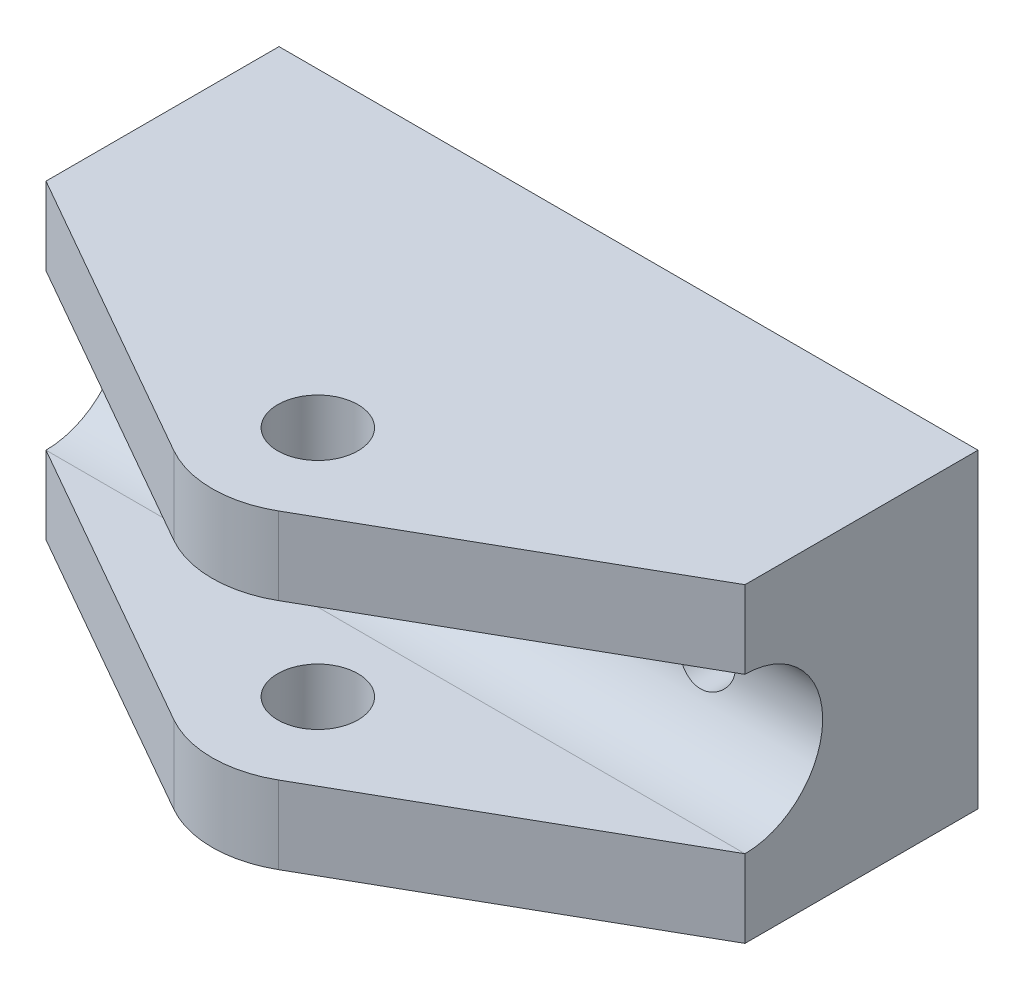
SolidWorks part; units mm, degrees
ref_plane "Front Plane" through (0, 0, 0) normal (0, 0, 1) x (1, 0, 0)
ref_plane "Top Plane" through (0, 0, 0) normal (0, 1, 0) x (1, 0, 0)
ref_plane "Right Plane" through (0, 0, 0) normal (1, 0, 0) x (0, 0, -1)
sketch "Sketch1" plane through (0, 0, 0) normal (0, 0, 1) x (1, 0, 0)
  line L1 (254.9308, 254) -> (197.7808, 254)
  line L2 (254.9308, 254) -> (254.9308, 228.6)
  line L3 (254.9308, 228.6) -> (197.7808, 228.6)
  line L4 (197.7808, 254) -> (197.7808, 228.6)
  line L5 (254.9308, 254) -> (197.7808, 228.6) construction
  line L6 (254.9308, 228.6) -> (197.7808, 254) construction
  line L11 (264.4558, 254) -> (-34.0111, 254) construction
  line L12 (264.4558, 228.6) -> (-34.0111, 228.6) construction
  line L13 (207.3058, 241.3) -> (245.4058, 241.3)
  circle A0 centre (245.4058, 241.3) radius 2.3813 construction
  circle A1 centre (207.3058, 241.3) radius 2.3813 construction
  circle A2 centre (245.4058, 241.3) radius 2.3813
  circle A3 centre (207.3058, 241.3) radius 2.3813
  point P6 (226.3558, 241.3)
  point P12 (226.3558, 241.3)
  dimension "D1" = 57.15
extrude "Boss-Extrude1" add sketch "Sketch1" along normal blind 34.036 contours L1 L4 L3 L2 A3 A2 region at (254.3054, 241.3, 0)
sketch "Sketch2" plane through (0, 254, 0) normal (0, 1, 0) x (1, 0, 0)
  line L0 (254.9308, -19.05) -> (230.633, -32.9024)
  line L1 (197.7808, -19.05) -> (222.0786, -32.9024)
  line L2 (254.9308, -34.036) -> (226.6818, -42.3141)
  line L3 (226.6818, -42.3141) -> (197.7808, -34.036)
  line L4 (254.9308, 0) -> (197.7808, 0)
  line L5 (197.7808, 0) -> (197.7808, -34.036)
  line L6 (197.7808, -34.036) -> (254.9308, -34.036)
  line L7 (254.9308, -34.036) -> (254.9308, 0)
  line L8 (254.9308, 0) -> (197.7808, 0)
  line L9 (197.7808, 0) -> (197.7808, -34.036)
  line L10 (197.7808, -34.036) -> (254.9308, -34.036) construction
  line L11 (254.9308, -34.036) -> (254.9308, 0)
  arc A0 (230.633, -32.9024) -> (222.0786, -32.9024) centre (226.3558, -25.4) cw
  circle A1 centre (226.3558, -25.4) radius 3.2814
  line M8 (197.7808, 0) -> (197.7808, -34.036)
  line M9 (197.7808, -34.036) -> (254.9308, -34.036)
  line M10 (254.9308, -34.036) -> (254.9308, 0)
  dimension "D2" = 19.05
  dimension "D3" = 25.4
  dimension "D1" = 0
extrude "Cut-Extrude1" cut sketch "Sketch2" against normal through all contours L0 A0 M9 M10 | A0 L1 M9 M8 | L3 L2 M9 | A1 region at (246.1291, 254, 29.0514) region at (226.4645, 254, 36.7954) region at (206.5824, 254, 29.0514) region at (226.3558, 254, 25.4)
sketch "Sketch3" plane through (197.7808, 0, 0) normal (-1, 0, 0) x (0, 0, 1)
  line L0 (19.05, 241.3) -> (49.022, 241.3) construction
  line L1 (19.05, 247.65) -> (49.022, 247.65)
  line L2 (19.05, 234.95) -> (49.022, 234.95)
  line L3 (34.036, 228.6) -> (34.036, 254) construction
  line L4 (19.05, 228.6) -> (19.05, 254) construction
  arc A0 (19.05, 247.65) -> (19.05, 234.95) centre (19.05, 241.3) ccw
  arc A1 (49.022, 234.95) -> (49.022, 247.65) centre (49.022, 241.3) ccw
  point P2 (34.036, 241.3)
  dimension "D1" = 6.35
extrude "Cut-Extrude2" cut sketch "Sketch3" against normal through all
ref_plane "Plane1" through (0, 241.3, 0) normal (0, -1, 0) x (-1, 0, 0)
sketch "Sketch4" plane through (0, 241.3, 0) normal (0, -1, 0) x (-1, 0, 0)
  circle A0 centre (-226.3558, -25.4) radius 3.2814 construction
  circle A1 centre (-226.3558, -25.4) radius 3.2814
  point P4 (-226.3558, -25.4)
ref_point "JOINT"
